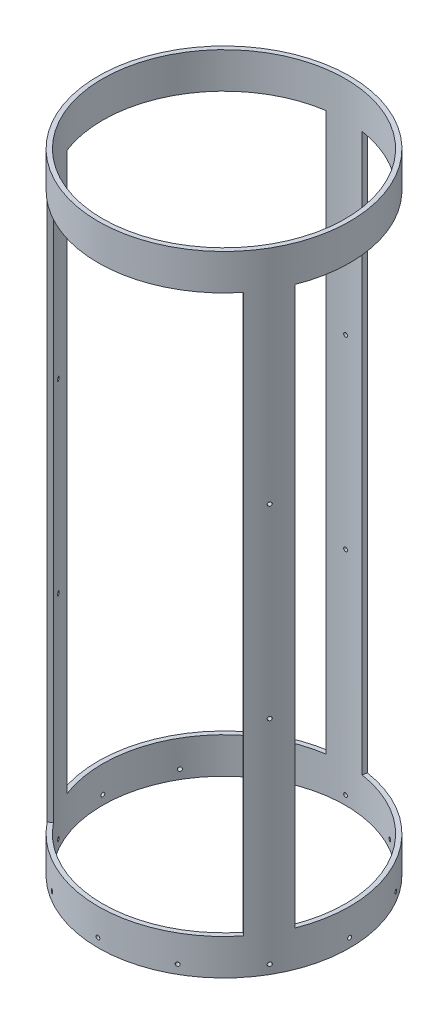
SolidWorks part; units mm, degrees
material "6061-T6 (SS)"
ref_plane "Front Plane" through (0, 0, 0) normal (0, 0, 1) x (1, 0, 0)
ref_plane "Top Plane" through (0, 0, 0) normal (0, 1, 0) x (1, 0, 0)
ref_plane "Right Plane" through (0, 0, 0) normal (1, 0, 0) x (0, 0, -1)
sketch "Sketch1" plane through (0, 0, 0) normal (0, 1, 0) x (1, 0, 0)
  circle A0 centre (0, 0) radius 88.9
  circle A1 centre (0, 0) radius 85.725
  dimension "D1" = 177.8
  dimension "D2" = 171.45
extrude "Boss-Extrude1" add sketch "Sketch1" along normal mid plane 444.5
sketch "Sketch6" plane through (0, -222.25, 0) normal (0, -1, 0) x (-1, 0, 0)
  line L0 (82.7901, -32.3885) -> (79.8333, -31.2317)
  line L1 (13.1222, 87.9262) -> (12.6536, 84.786)
  line L2 (0, 0) -> (0, 85.725) construction
  line L3 (-97.8543, 0) -> (97.8543, 0) construction
  line L4 (0, 0) -> (12.6536, 84.786) construction
  arc A0 (13.1222, 87.9262) -> (82.7901, -32.3885) centre (0, 0) cw
  circle A1 centre (0, 0) radius 88.9 construction
  arc A2 (12.6536, 84.786) -> (79.8333, -31.2317) centre (0, 0) cw
  circle A3 centre (0, 0) radius 85.725 construction
  arc A4 (0, 85.725) -> (12.6536, 84.786) centre (0, 0) cw construction
  dimension "D1" = 153.924
  dimension "D2" = 12.7
extrude "Cut-Extrude5" cut sketch "Sketch6" against normal offset from surface (393.7 mm away) 25.4 from offset 25.4 up to face at (0, 222.25, 88.9) offset against normal yes
pattern_circular "CirPattern5" count 3 over 360 about axis through (0, -222.25, 0) along (0, 1, 0) of "Cut-Extrude5"
ref_plane "Plane1" through (0, 0, -88.9) normal (0, 0, -1) x (-1, 0, 0)
sketch "Sketch3" plane through (0, 0, 0) normal (0, 0, -1) x (-1, 0, 0)
  line L1 (-88.9, -222.25) -> (88.9, -222.25) construction
  line L3 (-12.8692, 196.85) -> (-12.8692, -196.85) construction
  circle A0 centre (-0.1692, -215.9) radius 1.3525
  dimension "D1" = 6.35
  dimension "D2" = 2.7051
  dimension "D4" = 12.7
extrude "Cut-Extrude2" cut sketch "Sketch3" along normal up to surface (88.8921 mm away) up to face at (-0.0918, 0, 72.1578)
pattern_circular "CirPattern2" count 12 over 360 about axis through (0, 222.25, 0) along (0, -1, 0) of "Cut-Extrude2" reverse direction yes
sketch "Sketch4" plane through (0, 0, -88.9) normal (0, 0, -1) x (-1, 0, 0)
  line L1 (88.9, 222.25) -> (-88.9, 222.25) construction
  circle A0 centre (-0.1692, 215.9) radius 1.3525
  dimension "D1" = 2.7051
  dimension "D2" = 6.35
ref_plane "Plane2" through (0, 0, 88.9) normal (0, 0, 1) x (1, 0, 0)
sketch "Sketch5" plane through (0, 0, 88.9) normal (0, 0, 1) x (1, 0, 0)
  line L0 (-88.9, 196.85) -> (-13.1222, 196.85) construction
  line L1 (88.9, -196.85) -> (13.3458, -196.85) construction
  circle A0 centre (0.1692, 65.6167) radius 1.3526
  circle A1 centre (0.1692, -65.6167) radius 1.3526
  dimension "D1" = 131.2333
  dimension "D2" = 131.2333
  dimension "D3" = 2.7051
  dimension "D4" = 2.7051
extrude "Cut-Extrude4" cut sketch "Sketch5" against normal up to surface (177.787 mm away) up to face at (-0.0918, 0, 72.1578)
pattern_circular "CirPattern4" count 3 over 360 about axis through (0, 222.25, 0) along (0, -1, 0) of "Cut-Extrude4"
